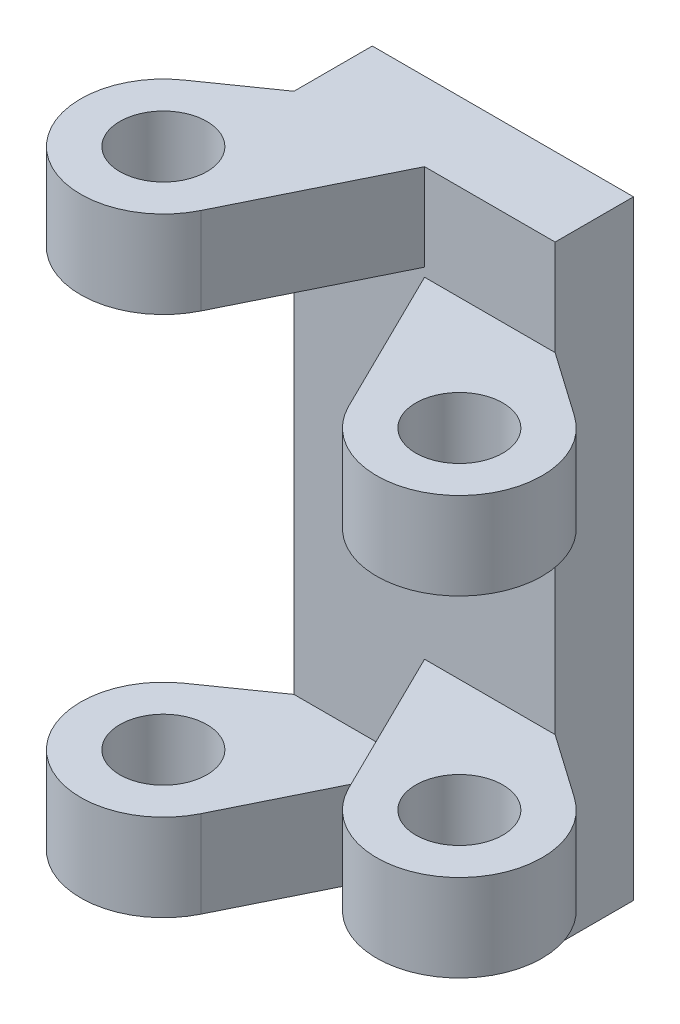
SolidWorks part; units mm, degrees
ref_plane "前视基准面" through (0, 0, 0) normal (0, 0, 1) x (1, 0, 0)
ref_plane "上视基准面" through (0, 0, 0) normal (0, 1, 0) x (1, 0, 0)
ref_plane "右视基准面" through (0, 0, 0) normal (1, 0, 0) x (0, 0, -1)
sketch "草图1" plane through (0, 0, 0) normal (0, 1, 0) x (1, 0, 0)
  line L0 (0, -1.8) -> (-1.4901, -2.8438)
  line L1 (0, 0) -> (6, 0)
  line L2 (0, 0) -> (0, -1.8)
  line L3 (0, -1.8) -> (6, -1.8)
  line L4 (6, 0) -> (6, -1.8)
  line L5 (1.3042, -5.2401) -> (3, -1.8)
  line L6 (4.6958, -5.2401) -> (3, -1.8)
  line L7 (7.4901, -2.8438) -> (6, -1.8)
  line L8 (-0.4, -4.4) -> (6.4, -4.4) construction
  line L9 (3, -4.4) -> (3, -1.8) construction
  circle A0 centre (-0.4, -4.4) radius 1.9
  circle A1 centre (6.4, -4.4) radius 1.9
  circle A2 centre (-0.4, -4.4) radius 1
  circle A3 centre (6.4, -4.4) radius 1
  dimension "D3" = 3.8
  dimension "D5" = 2
  dimension "D6" = 2
  dimension "D1" = 6
  dimension "D2" = 1.8
  dimension "D4" = 2.6
  dimension "D7" = 6.8
extrude "凸台-拉伸1" add sketch "草图1" along normal blind 7 and the other way blind 7 contours L4 L1 L2 L3 | A0 L5 L3 L0 | A1 L7 L3 L6 | A1 A3 | A0 A2 region at (1.3435, 0, 2.6406) region at (3, 0, 0.9) region at (0.4523, 0, 2.7623) region at (4.6565, 0, 2.6406) region at (5.1981, 0, 2.9985)
sketch "草图2" plane through (0, 0, 0) normal (0, 1, 0) x (1, 0, 0)
  line L0 (1.3042, -5.2401) -> (3, -1.8) construction
  line L2 (0, -1.8) -> (-1.4901, -2.8438) construction
  line L3 (0, -1.8) -> (3, -1.8)
  line L4 (1.3042, -5.2401) -> (3, -1.8)
  line L5 (0, -1.8) -> (-1.4901, -2.8438)
  arc A0 (-1.4901, -2.8438) -> (1.3042, -5.2401) centre (-0.4, -4.4) ccw construction
  arc A1 (-1.4901, -2.8438) -> (1.3042, -5.2401) centre (-0.4, -4.4) ccw
extrude "切除-拉伸1" cut sketch "草图2" against normal blind 5 and the other way blind 5
sketch "草图3" plane through (0, 0, 0) normal (0, 1, 0) x (1, 0, 0)
  line L0 (4.6958, -5.2401) -> (3, -1.8) construction
  line L1 (4.6958, -5.2401) -> (3, -1.8)
  line L2 (7.4901, -2.8438) -> (6, -1.8) construction
  line L3 (7.4901, -2.8438) -> (6, -1.8)
  line L4 (3, -1.8) -> (6, -1.8)
  arc A0 (4.6958, -5.2401) -> (7.4901, -2.8438) centre (6.4, -4.4) ccw construction
  arc A1 (4.6958, -5.2401) -> (7.4901, -2.8438) centre (6.4, -4.4) ccw
extrude "切除-拉伸2" cut sketch "草图3" against normal blind 2.8 and the other way blind 2.8
sketch "草图4" plane through (0, 7, 0) normal (0, 1, 0) x (1, 0, 0)
  line L0 (7.4901, -2.8438) -> (6, -1.8) construction
  line L1 (4.6958, -5.2401) -> (3, -1.8) construction
  line L2 (7.4901, -2.8438) -> (6, -1.8)
  line L3 (4.6958, -5.2401) -> (3, -1.8)
  line L4 (3, -1.8) -> (6, -1.8)
  arc A0 (4.6958, -5.2401) -> (7.4901, -2.8438) centre (6.4, -4.4) ccw construction
  arc A1 (4.6958, -5.2401) -> (7.4901, -2.8438) centre (6.4, -4.4) ccw
extrude "切除-拉伸3" cut sketch "草图4" against normal blind 2.2
mirror "镜向1" about plane through (0, 0, 0) normal (0, 1, 0) of "切除-拉伸3"
